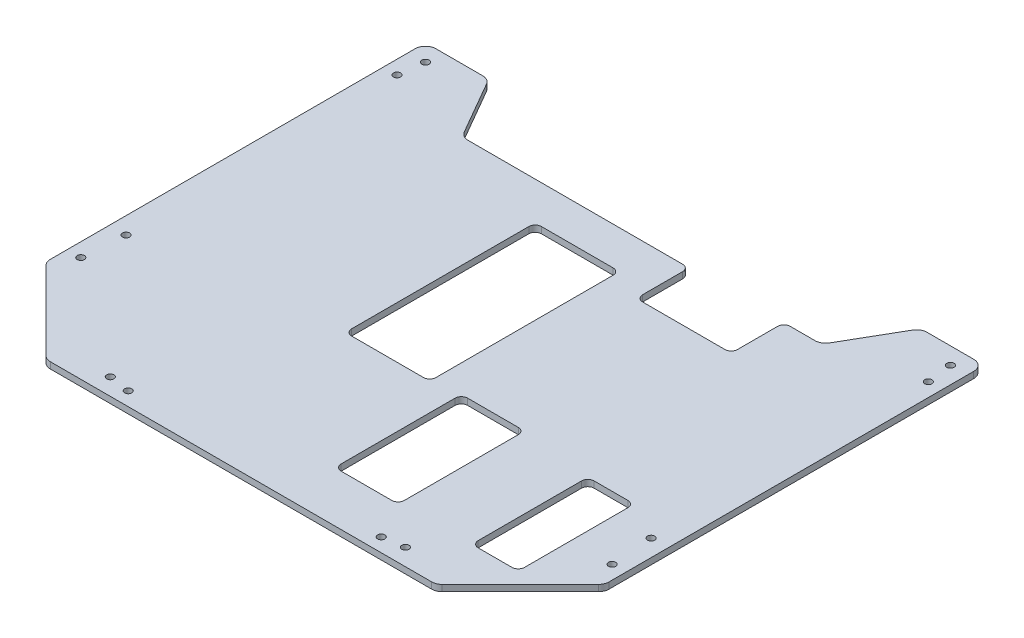
SolidWorks part; units mm, degrees
material "Acier non allié"
ref_plane "Front" through (0, 0, 0) normal (0, 0, 1) x (1, 0, 0)
ref_plane "Top" through (0, 0, 0) normal (0, 1, 0) x (1, 0, 0)
ref_plane "Right" through (0, 0, 0) normal (1, 0, 0) x (0, 0, -1)
sketch "Esquisse1" plane through (0, 0, 0) normal (0, 1, 0) x (1, 0, 0)
  line L0 (0, 0) -> (0, 1919.0564) construction
  line L1 (-92.5, 0) -> (92.5, 0)
  line L2 (92.5, 0) -> (132.5, 40)
  line L3 (132.5, 40) -> (132.5, 220)
  line L4 (132.5, 220) -> (102.5, 220)
  line L5 (102.5, 220) -> (85.1795, 190)
  line L6 (85.1795, 190) -> (-85.1795, 190)
  line L7 (-102.5, 220) -> (-85.1795, 190)
  line L8 (-132.5, 220) -> (-102.5, 220)
  line L9 (-132.5, 40) -> (-132.5, 220)
  line L10 (-92.5, 0) -> (-132.5, 40)
  point P12 (0, 190)
  dimension "D1" = 132.5
  dimension "D2" = 220
  dimension "D3" = 30
  dimension "D4" = 30
  dimension "D5" = 40
  dimension "D6" = 40
  dimension "D7" = 60
extrude "Boss.-Extru.1" add sketch "Esquisse1" along normal blind 3
fillet "Congé1" radius 5 10 edges at (132.5, 1.5, -220) (102.5, 1.5, -220) (85.1795, 1.5, -190) (-85.1795, 1.5, -190) (-102.5, 1.5, -220) (-132.5, 1.5, -220) (-132.5, 1.5, -40) (-92.5, 1.5, 0) (92.5, 1.5, 0) (132.5, 1.5, -40)
sketch "Esquisse2" plane through (0, 0, 0) normal (0, -1, 0) x (1, 0, 0)
  line L0 (0, 0) -> (0, -330.9968) construction
  line L1 (-90.4289, 0) -> (90.4289, 0) construction
  line L2 (-105.3868, -220) -> (-127.5, -220) construction
  line L3 (-132.5, -215) -> (-132.5, -42.0711) construction
  line L4 (-90.4289, 0) -> (90.4289, 0) construction
  line L5 (132.5, -42.0711) -> (132.5, -215) construction
  circle A0 centre (-70, -8) radius 1
  circle A1 centre (-124.5, -70) radius 1
  circle A2 centre (-124.5, -212) radius 1
  circle A3 centre (124.5, -212) radius 1
  circle A4 centre (124.5, -70) radius 1
  circle A5 centre (70, -8) radius 1
  circle A6 centre (126, -50) radius 1.5
  circle A7 centre (126, -200) radius 1.5
  circle A8 centre (-60, -6.5) radius 1.5
  circle A9 centre (60, -6.5) radius 1.5
  circle A10 centre (-126, -50) radius 1.5
  circle A11 centre (-126, -200) radius 1.5
  dimension "D3" = 2
  dimension "D6" = 2
  dimension "D9" = 2
  dimension "D12" = 3
  dimension "D15" = 3
  dimension "D16" = 3
  dimension "D17" = 3
  dimension "D24" = 3
  dimension "D27" = 3
  dimension "D1" = 70
  dimension "D2" = 8
  dimension "D4" = 124.5
  dimension "D5" = 70
  dimension "D7" = 8
  dimension "D8" = 8
  dimension "D10" = 50
  dimension "D11" = 6.5
  dimension "D13" = 15
  dimension "D14" = 6.5
  dimension "D18" = 10
  dimension "D19" = 6.5
  dimension "D20" = 6.5
  dimension "D21" = 10
  dimension "D22" = 50
  dimension "D23" = 6.5
  dimension "D25" = 15
  dimension "D26" = 6.5
extrude "Enlèv. mat.-Extru.1" cut sketch "Esquisse2" against normal through all
hole_wizard "Dégagement M31" positions "Esquisse3" profile "Esquisse4" hole size "M3" standard "ISO" end condition through all
sketch "Esquisse3" plane through (0, 0, 0) normal (0, -1, 0) x (-1, 0, 0)
  point P0 (-70, 8)
  point P3 (-124.5, 70)
  point P6 (-124.5, 212)
  point P9 (124.5, 212)
  point P12 (124.5, 70)
  point P15 (70, 8)
  point P18 (-126, 200)
  point P21 (-126, 50)
  point P24 (-60, 6.5)
  point P27 (60, 6.5)
  point P44 (126, 50)
  point P49 (126, 200)
sketch "Esquisse4" plane through (70, 0, -8) normal (1, 0, 0) x (0, 0, -1)
  line L0 (0, 0) -> (0, 3)
  line L1 (0, 3) -> (1.7, 3)
  line L2 (1.7, 3) -> (1.7, 0)
  line L5 (1.7, 0) -> (0, 0)
  line L11 (0, -6.35) -> (0, 107.95) construction
  dimension "Diamètre du perçage jusqu'au prochain" = 3.4
  dimension "Profondeur du perçage jusqu'au prochain" = 3
sketch "Esquisse5" plane through (0, 0, 0) normal (0, -1, 0) x (1, 0, 0)
  line L6 (82.2927, -190) -> (-82.2927, -190) construction
  line L7 (22.5, -190) -> (67.5, -190)
  line L20 (22.5, -190) -> (22.5, -165)
  line L21 (22.5, -165) -> (67.5, -165)
  line L22 (67.5, -190) -> (67.5, -165)
  line L23 (132.5, -42.0711) -> (132.5, -215) construction
  line L25 (-32.5, -172) -> (7.5, -172)
  line L26 (-32.5, -172) -> (-32.5, -82)
  line L27 (-32.5, -82) -> (7.5, -82)
  line L28 (7.5, -172) -> (7.5, -82)
  line L29 (-132.5, -215) -> (-132.5, -42.0711) construction
  line L30 (127.5, -220) -> (105.3868, -220) construction
  line L31 (84.5, -80) -> (106.5, -80)
  line L32 (84.5, -80) -> (84.5, -25)
  line L33 (84.5, -25) -> (106.5, -25)
  line L34 (106.5, -80) -> (106.5, -25)
  line L35 (-90.4289, 0) -> (90.4289, 0) construction
  line L38 (20.5, -84) -> (50.5, -84)
  line L39 (20.5, -84) -> (20.5, -24)
  line L40 (20.5, -24) -> (50.5, -24)
  line L41 (50.5, -84) -> (50.5, -24)
  dimension "D14" = 24
  dimension "D12" = 60
  dimension "D1" = 65
  dimension "D2" = 110
  dimension "D3" = 25
  dimension "D4" = 82
  dimension "D5" = 140
  dimension "D6" = 90
  dimension "D7" = 40
  dimension "D8" = 48
  dimension "D9" = 140
  dimension "D10" = 55
  dimension "D11" = 22
  dimension "D13" = 30
  dimension "D15" = 82
extrude "Enlèv. mat.-Extru.2" cut sketch "Esquisse5" against normal through all
fillet "Congé2" radius 3 16 edges at (67.5, 1.5, -190) (67.5, 1.5, -165) (22.5, 1.5, -165) (22.5, 1.5, -190) (106.5, 1.5, -80) (84.5, 1.5, -80) (84.5, 1.5, -25) (106.5, 1.5, -25) (7.5, 1.5, -82) (7.5, 1.5, -172) (-32.5, 1.5, -82) (-32.5, 1.5, -172) (50.5, 1.5, -84) (20.5, 1.5, -84) (50.5, 1.5, -24) (20.5, 1.5, -24)
equation "\"WIDTH\"= 300mm'Total width of the robot"
equation "\"LENGTH\"= 220mm'Total length of the robot"
equation "\"CUT_DEPTH\"= 45mm'Depth of the cut on the edges of the plate"
equation "\"Plate_th\"= 3mm'Thickness of the plate"
equation "\"D1\"= \"Plate_th\""
